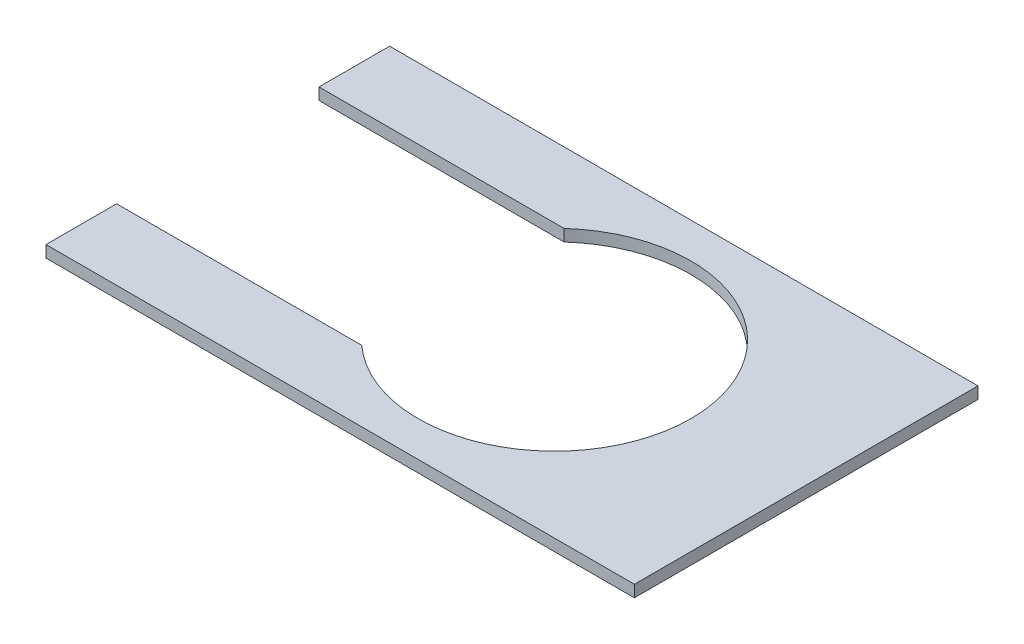
SolidWorks part; units mm, degrees
ref_plane "Front Plane" through (0, 0, 0) normal (0, 0, 1) x (1, 0, 0)
ref_plane "Top Plane" through (0, 0, 0) normal (0, 1, 0) x (1, 0, 0)
ref_plane "Right Plane" through (0, 0, 0) normal (1, 0, 0) x (0, 0, -1)
sketch "Sketch1" plane through (0, 0, 0) normal (0, 1, 0) x (1, 0, 0)
  line L0 (-118.6638, 10) -> (-118.6638, -20) construction
  line L5 (-228.6638, 10) -> (-118.6638, 10)
  line L6 (-228.6638, 10) -> (-228.6638, -20)
  line L7 (-228.6638, -20) -> (-124.5174, -20)
  line L11 (-118.6638, 10) -> (21.3362, 10)
  line L12 (21.3362, -106) -> (21.3362, 10)
  line L13 (-118.6638, -20) -> (-118.6638, -106) construction
  line L14 (-118.6638, -63) -> (-88.6227, -63) construction
  line L24 (-183.6227, -20) -> (-183.6227, -106) construction
  line L26 (21.3362, -106) -> (21.3362, -136)
  line L28 (-118.6638, -136) -> (21.3362, -136)
  line L29 (-228.6638, -136) -> (-118.6638, -136)
  line L30 (-228.6638, -136) -> (-228.6638, -106)
  line L31 (-228.6638, -106) -> (-124.5174, -106)
  line L34 (-73.6638, -20) -> (-73.6638, -106) construction
  arc A2 (-158.108, -20) -> (-209.1375, -20) centre (-183.6227, -63) ccw construction
  arc A6 (-124.5174, -106) -> (-124.5174, -20) centre (-85.5944, -63) ccw
  circle A7 centre (-183.6227, -63) radius 43 construction
  circle A8 centre (-183.6227, -63) radius 61.8136 construction
  point P24 (-183.6227, -63)
  dimension "D7" = 116
  dimension "D1" = 110
  dimension "D2" = 30
  dimension "D3" = 86
  dimension "D5" = 140
extrude "Boss-Extrude1" add sketch "Sketch1" along normal blind 5
sketch "Sketch3" plane through (0, 0, 20) normal (0, 0, 1) x (1, 0, 0)
  line L0 (-228.6638, 5) -> (-228.6638, 0) construction
  line L1 (-228.6638, 5) -> (-206.346, 5)
  line L2 (-228.6638, 5) -> (-228.6638, 2.5)
  line L3 (-228.6638, 2.5) -> (-206.346, 2.5)
  line L4 (-206.346, 5) -> (-206.346, 2.5)
  line L5 (-228.6638, 5) -> (-124.5174, 5) construction
  dimension "D1" = 2.5
